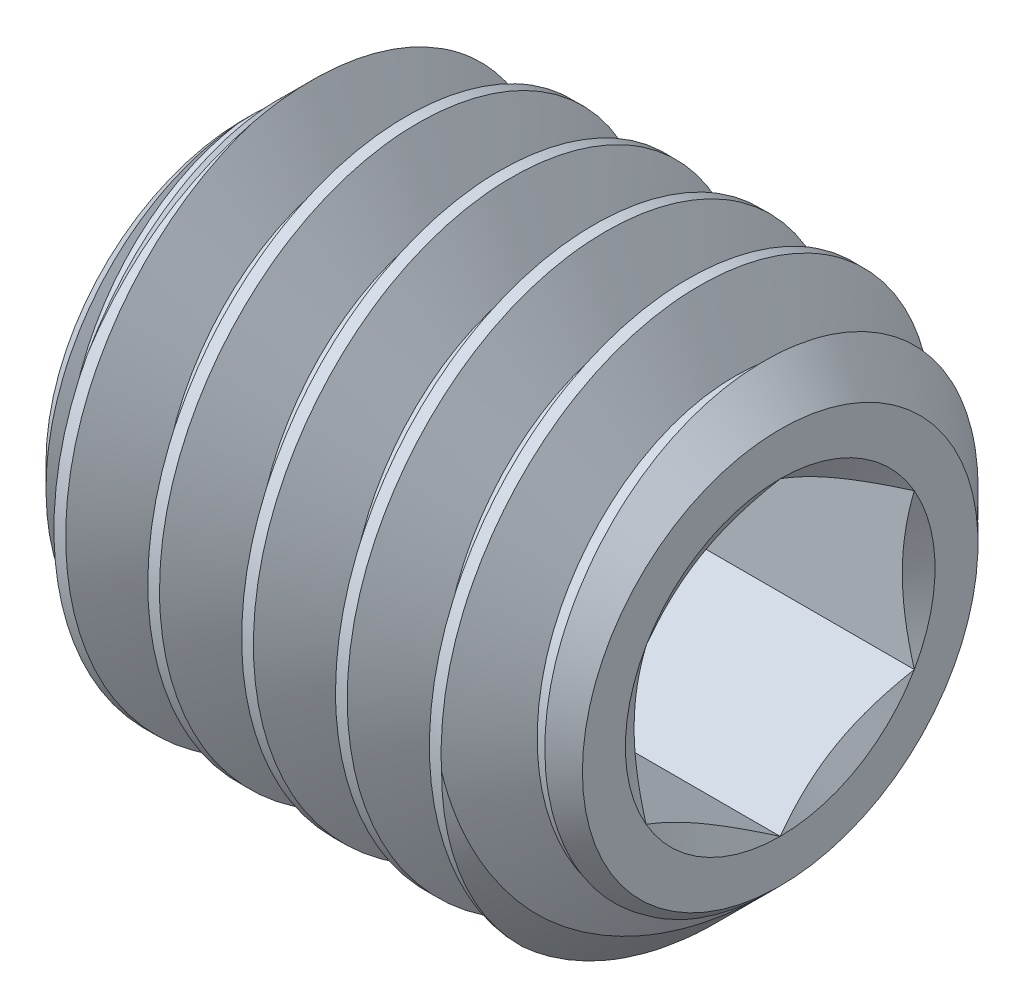
SolidWorks part; units mm, degrees
material "Plain Carbon Steel"
ref_plane "Front Plane" through (0, 0, 0) normal (0, 0, 1) x (1, 0, 0)
ref_plane "Top Plane" through (0, 0, 0) normal (0, 1, 0) x (1, 0, 0)
ref_plane "Right Plane" through (0, 0, 0) normal (1, 0, 0) x (0, 0, -1)
sketch "Sketch1" plane through (0, 0, 0) normal (0, 0, 1) x (1, 0, 0)
  line L0 (2, 2) -> (2, -2) construction
  line L1 (2, 2) -> (-2, 2) construction
  line L2 (-2, 2) -> (-2, -2) construction
  line L3 (-2, -2) -> (2, -2) construction
  line L4 (-2, 0) -> (2, 0) construction
  line L5 (1.475, 2) -> (2, 1.475) construction
  line L6 (2, -1.475) -> (1.475, -2) construction
  line L7 (-1.475, 2) -> (-2, 1.475) construction
  line L8 (-2, -1.475) -> (-1.475, -2) construction
  line L9 (1.9562, 2.0758) -> (2.6562, 2.0758) construction
  line L10 (2.6562, 2.0758) -> (2.3062, 1.4696) construction
  line L11 (2.3062, 1.4696) -> (1.9562, 2.0758) construction
  line L12 (2.3062, 1.4696) -> (2.3062, 1.5453) construction
  line L13 (1.9781, 2.0379) -> (2.6344, 2.0379) construction
  line L14 (2.3062, 2) -> (2.3062, 2.0758) construction
  line L16 (2.6125, 2) -> (2, 2) construction
  line L18 (2.2625, 1.5453) -> (2.35, 1.5453) construction
  point P2 (1.3, 2)
  point P16 (0.25, -2)
  point P17 (2, 1)
  point P25 (2.3062, 2.0379)
  dimension "Thread Pitch" = 0.7
  dimension "Thread Size" = 4
  dimension "D3" = 45
  dimension "Length" = 4
  dimension "D5" = 0.525
  dimension "Drive Size" = 2
  dimension "D1" = 1.75
  dimension "D2" = 0.7
  dimension "D4" = 0.0875
sketch "Sketch2" plane through (0, 0, 0) normal (0, 0, 1) x (1, 0, 0)
  line L0 (-2, 0) -> (-2, 1.475)
  line L1 (-2, 1.475) -> (-1.475, 2)
  line L2 (-1.475, 2) -> (1.475, 2)
  line L3 (1.475, 2) -> (2, 1.475)
  line L4 (2, 1.475) -> (2, 0)
  line L5 (2, 0) -> (-2, 0)
revolve "Revolve1" add sketch "Sketch2" angle 360 about L4
sketch "Sketch3" plane through (2, 0, 0) normal (1, 0, 0) x (0, 0, -1)
  line L0 (0, 2) -> (0, -2) construction
  line L1 (-1, -0.5774) -> (0, -1.1547)
  line L2 (0, -1.1547) -> (1, -0.5774)
  line L3 (1, -0.5774) -> (1, 0.5774)
  line L4 (1, 0.5774) -> (0, 1.1547)
  line L5 (0, 1.1547) -> (-1, 0.5774)
  line L6 (-1, 0.5774) -> (-1, -0.5774)
  circle A0 centre (0, 0) radius 1 construction
extrude "Cut-Extrude1" cut sketch "Sketch3" against normal blind 2
sketch "Sketch4" plane through (2, 0, 0) normal (1, 0, 0) x (0, 0, -1)
  circle A0 centre (0, 0) radius 1.1547
extrude "Cut-Extrude2" cut sketch "Sketch4" against normal through all draft 60
sketch "Sketch6" plane through (-2, 0, 0) normal (1, 0, 0) x (0, 0, -1)
  line L0 (0, 2) -> (0, -2) construction
  circle A0 centre (0, 0) radius 2
curve "Helix/Spiral1" pitch 0.7 height 5.4 radius 2 centre (-2, 0, 0) axis (-1, 0, 0) start towards (0, 1, 0)
sketch "Sketch7" plane through (0, 0, 0) normal (0, 0, 1) x (1, 0, 0)
  line L0 (1.9781, 2.0379) -> (2.2625, 1.5453)
  line L1 (2.2625, 1.5453) -> (2.35, 1.5453)
  line L2 (2.35, 1.5453) -> (2.6344, 2.0379)
  line L3 (2.6344, 2.0379) -> (1.9781, 2.0379)
sweep "Cut-Sweep4" cut profiles "Sketch7" path "Helix/Spiral1"
equation "\"D5@Sketch1\"=\"Thread Pitch@Sketch1\"*.75"
equation "\"D1@Cut-Extrude1\"=\"Drive Size@Sketch1\""
equation "\"D3@Helix/Spiral1\"=2*\"Thread Pitch@Sketch1\"+\"Length@Sketch1\""
equation "\"D4@Helix/Spiral1\"=\"Thread Pitch@Sketch1\""
equation "\"D1@Sketch1\"=\"Thread Pitch@Sketch1\"*2.5"
equation "\"D2@Sketch1\"=\"Thread Pitch@Sketch1\""
equation "\"D4@Sketch1\"=\"Thread Pitch@Sketch1\"/8"
